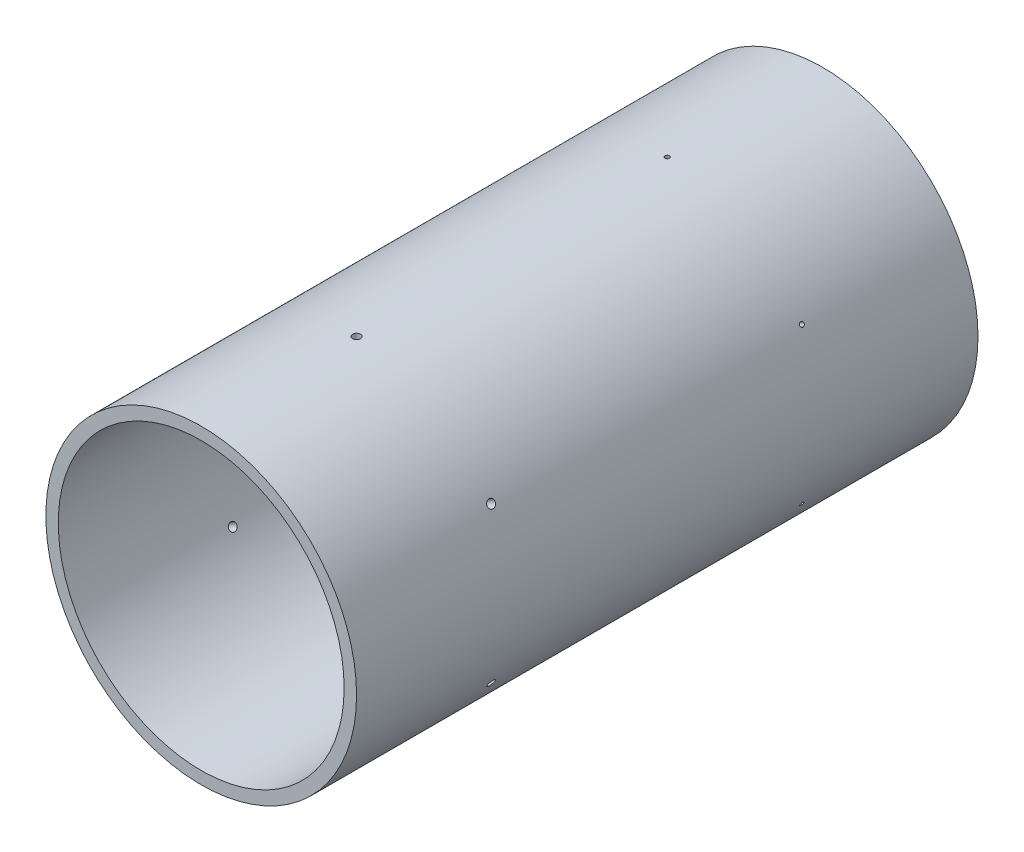
SolidWorks part; units mm, degrees
ref_plane "Front Plane" through (0, 0, 0) normal (0, 0, 1) x (1, 0, 0)
ref_plane "Top Plane" through (0, 0, 0) normal (0, 1, 0) x (1, 0, 0)
ref_plane "Right Plane" through (0, 0, 0) normal (1, 0, 0) x (0, 0, -1)
sketch "Sketch1" plane through (0, 0, 0) normal (0, 0, 1) x (1, 0, 0)
  circle A0 centre (0, 0) radius 79.375
  circle A1 centre (0, 0) radius 73.025
  dimension "D1" = 158.75
  dimension "D2" = 6.35
extrude "Boss-Extrude1" add sketch "Sketch1" along normal blind 317.5
ref_plane "Plane1" through (0, 79.375, 0) normal (0, 1, 0) x (1, 0, 0)
sketch "Sketch2" plane through (0, 79.375, 0) normal (0, 1, 0) x (1, 0, 0)
  line L0 (79.375, 0) -> (-79.375, 0) construction
  point P0 (0, -79.375)
  dimension "D1" = 79.375
hole_wizard "#4-40 Tapped Hole1" positions "Sketch5" profile "Sketch6" tap size "#4-40" standard "ANSI Inch" end condition up to next
sketch "Sketch5" plane through (0, 79.375, 0) normal (0, 1, 0) x (1, 0, 0)
  point P0 (0, -79.375)
sketch "Sketch6" plane through (0, 79.375, 79.375) normal (1, 0, 0) x (0, 0, 1)
  line L0 (0, 0) -> (0, 6.35)
  line L1 (0, 6.35) -> (1.1303, 6.35)
  line L2 (1.1303, 6.35) -> (1.1303, 0)
  line L5 (1.1303, 0) -> (0, 0)
  line L11 (0, -6.35) -> (0, 107.95) construction
  dimension "Thru Tap Drill Dia." = 2.2606
  dimension "Thru Tap Drill Depth" = 6.35
cosmetic thread "Hole Thread1"
sketch "Sketch7" plane through (0, 79.375, 0) normal (0, 1, 0) x (1, 0, 0)
  line L0 (-79.375, -317.5) -> (79.375, -317.5) construction
  point P0 (0, -238.125)
  dimension "D1" = 79.375
hole_wizard "#10-32 Tapped Hole1" positions "Sketch8" profile "Sketch9" tap size "#10-32" standard "ANSI Inch" end condition up to next
sketch "Sketch8" plane through (0, 79.375, 0) normal (0, 1, 0) x (1, 0, 0)
  point P0 (0, -238.125)
sketch "Sketch9" plane through (0, 79.375, 238.125) normal (1, 0, 0) x (0, 0, 1)
  line L0 (0, 0) -> (0, 6.35)
  line L1 (0, 6.35) -> (2.0193, 6.35)
  line L2 (2.0193, 6.35) -> (2.0193, 0)
  line L5 (2.0193, 0) -> (0, 0)
  line L11 (0, -6.35) -> (0, 107.95) construction
  dimension "Thru Tap Drill Dia." = 4.0386
  dimension "Thru Tap Drill Depth" = 6.35
cosmetic thread "Hole Thread2"
pattern_circular "CirPattern1" count 6 over 360 about axis through (0, 0, 317.5) along (0, 0, 1) of "#4-40 Tapped Hole1", "#10-32 Tapped Hole1"
cosmetic thread "Hole Thread3"
cosmetic thread "Hole Thread4"
cosmetic thread "Hole Thread5"
cosmetic thread "Hole Thread6"
cosmetic thread "Hole Thread7"
cosmetic thread "Hole Thread8"
cosmetic thread "Hole Thread9"
cosmetic thread "Hole Thread10"
cosmetic thread "Hole Thread11"
cosmetic thread "Hole Thread12"
